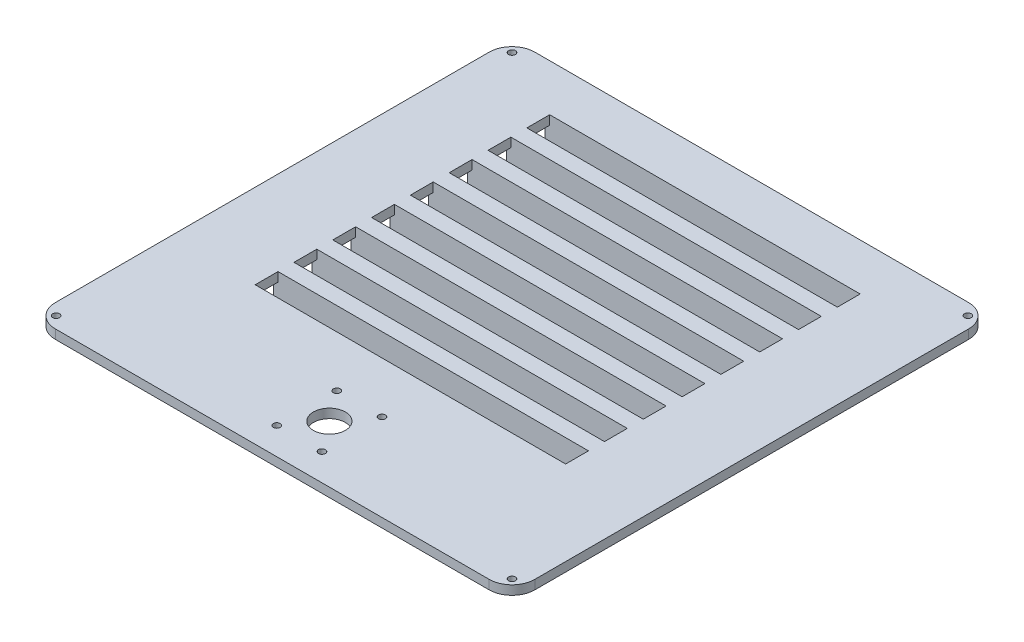
SolidWorks part; units mm, degrees
ref_plane "Front Plane" through (0, 0, 0) normal (0, 0, 1) x (1, 0, 0)
ref_plane "Top Plane" through (0, 0, 0) normal (0, 1, 0) x (1, 0, 0)
ref_plane "Right Plane" through (0, 0, 0) normal (1, 0, 0) x (0, 0, -1)
sketch "Sketch1" plane through (0, 0, 0) normal (0, 1, 0) x (1, 0, 0)
  line L0 (-101, -101) -> (-101, 101)
  line L5 (-105, -105) -> (105, -105)
  line L6 (-105, -105) -> (-105, 105)
  line L7 (-105, 105) -> (105, 105)
  line L8 (105, -105) -> (105, 105)
  line L9 (-101, 101) -> (101, 101)
  line L10 (101, -101) -> (101, 101)
  line L11 (-101, -101) -> (101, -101)
  line L12 (-101, 101) -> (-99.8333, 99.8333) construction
  line L13 (-55, 0) -> (55, 0) construction
  line L14 (-101, -101) -> (-99.8333, -99.8333) construction
  line L15 (0, -55) -> (0, 55) construction
  line L16 (101, -101) -> (99.8333, -99.8333) construction
  line L17 (101, 101) -> (99.8333, 99.8333) construction
  circle A1 centre (-99.8333, 99.8333) radius 1.5
  circle A2 centre (-99.8333, -99.8333) radius 1.5
  circle A3 centre (99.8333, -99.8333) radius 1.5
  circle A4 centre (99.8333, 99.8333) radius 1.5
  point P0 (0, 0)
  point P6 (-105, 0)
  point P7 (0, 105)
  dimension "D3" = 4
  dimension "D4" = 3
  dimension "D1" = 210
  dimension "D2" = 210
  dimension "D5" = 1.65
  dimension "D6" = 45
extrude "MainExtrude" add sketch "Sketch1" along normal blind 4 contours L6 L5 L8 L7
extrude "ScrewHoles" cut sketch "Sketch1<6>" along normal up to surface (4 mm away) contours A1 | A2 | A3 | A4 up to face at (0, 4, 0)
sketch "Sketch1<6>" plane through (0, 0, 0) normal (0, 1, 0) x (1, 0, 0) same geometry as "Sketch1"
fillet "RoundedCorners" radius 10 4 edges at (-105, 2, -105) (-105, 2, 105) (105, 2, -105) (105, 2, 105)
sketch "Sketch3" plane through (0, 0, 0) normal (0, 1, 0) x (1, 0, 0)
  line L145 (-68, 96.5) -> (68, 96.5) construction
  line L146 (-68, 96.5) -> (-68, -56.5) construction
  line L147 (-68, -56.5) -> (68, -56.5) construction
  line L148 (68, 96.5) -> (68, -56.5) construction
  line L149 (-68, 96.5) -> (68, -56.5) construction
  line L151 (68, 96.5) -> (-68, -56.5) construction
  line L152 (-68, 79.5) -> (68, 79.5) construction
  line L154 (-68, 62.5) -> (68, 62.5) construction
  line L155 (-68, 45.5) -> (68, 45.5) construction
  line L157 (-68, 28.5) -> (68, 28.5) construction
  line L158 (-68, 11.5) -> (68, 11.5) construction
  line L159 (-68, -5.5) -> (68, -5.5) construction
  line L160 (-68, -22.5) -> (68, -22.5) construction
  line L161 (-68, -39.5) -> (68, -39.5) construction
  line L162 (-68, 74.5) -> (68, 74.5)
  line L163 (-68, 57.5) -> (68, 57.5)
  line L164 (-68, 40.5) -> (68, 40.5)
  line L165 (-68, 23.5) -> (68, 23.5)
  line L166 (-68, 6.5) -> (68, 6.5)
  line L167 (-68, -10.5) -> (68, -10.5)
  line L168 (-68, -27.5) -> (68, -27.5)
  line L169 (-68, -44.5) -> (68, -44.5)
  line L170 (-68, 84.5) -> (68, 84.5)
  line L171 (-68, 67.5) -> (68, 67.5)
  line L172 (-68, 50.5) -> (68, 50.5)
  line L173 (-68, 33.5) -> (68, 33.5)
  line L174 (-68, 16.5) -> (68, 16.5)
  line L175 (-68, -0.5) -> (68, -0.5)
  line L176 (-68, -17.5) -> (68, -17.5)
  line L177 (-68, -34.5) -> (68, -34.5)
  line L178 (-68, 74.5) -> (-68, 84.5)
  line L179 (68, 74.5) -> (68, 84.5)
  line L180 (-68, 57.5) -> (-68, 67.5)
  line L181 (68, 57.5) -> (68, 67.5)
  line L182 (-68, 40.5) -> (-68, 50.5)
  line L183 (68, 40.5) -> (68, 50.5)
  line L184 (-68, 23.5) -> (-68, 33.5)
  line L185 (68, 23.5) -> (68, 33.5)
  line L186 (-68, 6.5) -> (-68, 16.5)
  line L187 (68, 6.5) -> (68, 16.5)
  line L188 (-68, -10.5) -> (-68, -0.5)
  line L189 (68, -10.5) -> (68, -0.5)
  line L190 (-68, -27.5) -> (-68, -17.5)
  line L191 (68, -27.5) -> (68, -17.5)
  line L192 (-68, -44.5) -> (-68, -34.5)
  line L193 (68, -44.5) -> (68, -34.5)
  line L200 (-9.9, -66.85) -> (-9.9, -93.15) construction
  line L201 (-95, -105) -> (95, -105) construction
  line L207 (-97.2358, 20) -> (95.5763, 20) construction
  line L208 (-9.9, -66.85) -> (9.9, -66.85) construction
  circle A0 centre (0, -80) radius 7
  circle A1 centre (-9.9, -66.85) radius 1.5
  circle A2 centre (-9.9, -93.15) radius 1.5
  circle A3 centre (9.9, -93.15) radius 1.5
  circle A4 centre (9.9, -66.85) radius 1.5
  point P56 (-9.9, -80)
  point P69 (0, -66.85)
  point P70 (0, 20)
  dimension "D18" = 14
  dimension "D19" = 25
  dimension "D21" = 35.5
  dimension "D25" = 3
  dimension "D26" = 3
  dimension "D27" = 19.8
  dimension "D1" = 136
  dimension "D2" = 153
  dimension "D3" = 17
  dimension "D4" = 17
  dimension "D5" = 17
  dimension "D6" = 17
  dimension "D7" = 17
  dimension "D8" = 17
  dimension "D9" = 17
  dimension "D11" = 17
  dimension "D13" = 5
  dimension "D14" = 129
  dimension "D10" = 17
  dimension "D12" = 5
  dimension "D20" = 20
  dimension "D28" = 26.3
extrude "Trench" cut sketch "Sketch3" along normal blind 10
sketch "Sketch4" plane through (0, 0, 0) normal (0, 1, 0) x (1, 0, 0)
  line L0 (68, -34.5) -> (68, -44.5) construction
  line L1 (68, -44.5) -> (-68, -44.5) construction
  line L2 (-68, -44.5) -> (-68, -34.5) construction
  line L3 (-68, -34.5) -> (68, -34.5) construction
  line L4 (68, -17.5) -> (68, -27.5) construction
  line L5 (68, -27.5) -> (-68, -27.5) construction
  line L6 (-68, -27.5) -> (-68, -17.5) construction
  line L7 (-68, -17.5) -> (68, -17.5) construction
  line L8 (68, -0.5) -> (68, -10.5) construction
  line L9 (68, -10.5) -> (-68, -10.5) construction
  line L10 (-68, -10.5) -> (-68, -0.5) construction
  line L11 (-68, -0.5) -> (68, -0.5) construction
  line L12 (68, 16.5) -> (68, 6.5) construction
  line L13 (68, 6.5) -> (-68, 6.5) construction
  line L14 (-68, 6.5) -> (-68, 16.5) construction
  line L15 (-68, 16.5) -> (68, 16.5) construction
  line L16 (68, 33.5) -> (68, 23.5) construction
  line L17 (68, 23.5) -> (-68, 23.5) construction
  line L18 (-68, 23.5) -> (-68, 33.5) construction
  line L19 (-68, 33.5) -> (68, 33.5) construction
  line L20 (68, 50.5) -> (68, 40.5) construction
  line L21 (68, 40.5) -> (-68, 40.5) construction
  line L22 (-68, 40.5) -> (-68, 50.5) construction
  line L23 (-68, 50.5) -> (68, 50.5) construction
  line L24 (68, 67.5) -> (68, 57.5) construction
  line L25 (68, 57.5) -> (-68, 57.5) construction
  line L26 (-68, 57.5) -> (-68, 67.5) construction
  line L27 (-68, 67.5) -> (68, 67.5) construction
  line L28 (68, 84.5) -> (68, 74.5) construction
  line L29 (68, 74.5) -> (-68, 74.5) construction
  line L30 (-68, 74.5) -> (-68, 84.5) construction
  line L31 (-68, 84.5) -> (68, 84.5) construction
  line L32 (68, -34.5) -> (68, -44.5)
  line L33 (68, -44.5) -> (-68, -44.5)
  line L34 (-68, -44.5) -> (-68, -34.5)
  line L35 (-68, -34.5) -> (68, -34.5)
  line L36 (68, -17.5) -> (68, -27.5)
  line L37 (68, -27.5) -> (-68, -27.5)
  line L38 (-68, -27.5) -> (-68, -17.5)
  line L39 (-68, -17.5) -> (68, -17.5)
  line L40 (68, -0.5) -> (68, -10.5)
  line L41 (68, -10.5) -> (-68, -10.5)
  line L42 (-68, -10.5) -> (-68, -0.5)
  line L43 (-68, -0.5) -> (68, -0.5)
  line L44 (68, 16.5) -> (68, 6.5)
  line L45 (68, 6.5) -> (-68, 6.5)
  line L46 (-68, 6.5) -> (-68, 16.5)
  line L47 (-68, 16.5) -> (68, 16.5)
  line L48 (68, 33.5) -> (68, 23.5)
  line L49 (68, 23.5) -> (-68, 23.5)
  line L50 (-68, 23.5) -> (-68, 33.5)
  line L51 (-68, 33.5) -> (68, 33.5)
  line L52 (68, 50.5) -> (68, 40.5)
  line L53 (68, 40.5) -> (-68, 40.5)
  line L54 (-68, 40.5) -> (-68, 50.5)
  line L55 (-68, 50.5) -> (68, 50.5)
  line L56 (68, 67.5) -> (68, 57.5)
  line L57 (68, 57.5) -> (-68, 57.5)
  line L58 (-68, 57.5) -> (-68, 67.5)
  line L59 (-68, 67.5) -> (68, 67.5)
  line L60 (68, 84.5) -> (68, 74.5)
  line L61 (68, 74.5) -> (-68, 74.5)
  line L62 (-68, 74.5) -> (-68, 84.5)
  line L63 (-68, 84.5) -> (68, 84.5)
  line L64 (70, 86.5) -> (70, 72.5)
  line L65 (70, 72.5) -> (-70, 72.5)
  line L66 (-70, 72.5) -> (-70, 86.5)
  line L67 (-70, 86.5) -> (70, 86.5)
  line L68 (70, 69.5) -> (70, 55.5)
  line L69 (70, 55.5) -> (-70, 55.5)
  line L70 (-70, 55.5) -> (-70, 69.5)
  line L71 (-70, 69.5) -> (70, 69.5)
  line L72 (70, 52.5) -> (70, 38.5)
  line L73 (70, 38.5) -> (-70, 38.5)
  line L74 (-70, 38.5) -> (-70, 52.5)
  line L75 (-70, 52.5) -> (70, 52.5)
  line L76 (70, 35.5) -> (70, 21.5)
  line L77 (70, 21.5) -> (-70, 21.5)
  line L78 (-70, 21.5) -> (-70, 35.5)
  line L79 (-70, 35.5) -> (70, 35.5)
  line L80 (70, 18.5) -> (70, 4.5)
  line L81 (70, 4.5) -> (-70, 4.5)
  line L82 (-70, 4.5) -> (-70, 18.5)
  line L83 (-70, 18.5) -> (70, 18.5)
  line L84 (70, 1.5) -> (70, -12.5)
  line L85 (70, -12.5) -> (-70, -12.5)
  line L86 (-70, -12.5) -> (-70, 1.5)
  line L87 (-70, 1.5) -> (70, 1.5)
  line L88 (70, -15.5) -> (70, -29.5)
  line L89 (70, -29.5) -> (-70, -29.5)
  line L90 (-70, -29.5) -> (-70, -15.5)
  line L91 (-70, -15.5) -> (70, -15.5)
  line L92 (70, -32.5) -> (70, -46.5)
  line L93 (70, -46.5) -> (-70, -46.5)
  line L94 (-70, -46.5) -> (-70, -32.5)
  line L95 (-70, -32.5) -> (70, -32.5)
  dimension "D1" = 2
extrude "Trench Walls" add sketch "Sketch4" against normal blind 4
sketch "Sketch5" plane through (0, -4, 0) normal (0, -1, 0) x (1, 0, 0)
  line L0 (-70, -86.5) -> (70, -86.5) construction
  line L1 (70, -86.5) -> (70, -72.5) construction
  line L2 (70, -72.5) -> (-70, -72.5) construction
  line L3 (-70, -72.5) -> (-70, -86.5) construction
  line L4 (-70, -69.5) -> (70, -69.5) construction
  line L5 (70, -69.5) -> (70, -55.5) construction
  line L6 (70, -55.5) -> (-70, -55.5) construction
  line L7 (-70, -55.5) -> (-70, -69.5) construction
  line L8 (-70, -52.5) -> (70, -52.5) construction
  line L9 (70, -52.5) -> (70, -38.5) construction
  line L10 (70, -38.5) -> (-70, -38.5) construction
  line L11 (-70, -38.5) -> (-70, -52.5) construction
  line L12 (-70, -35.5) -> (70, -35.5) construction
  line L13 (70, -35.5) -> (70, -21.5) construction
  line L14 (70, -21.5) -> (-70, -21.5) construction
  line L15 (-70, -21.5) -> (-70, -35.5) construction
  line L16 (-70, -18.5) -> (70, -18.5) construction
  line L17 (70, -18.5) -> (70, -4.5) construction
  line L18 (70, -4.5) -> (-70, -4.5) construction
  line L19 (-70, -4.5) -> (-70, -18.5) construction
  line L20 (-70, -1.5) -> (70, -1.5) construction
  line L21 (70, -1.5) -> (70, 12.5) construction
  line L22 (70, 12.5) -> (-70, 12.5) construction
  line L23 (-70, 12.5) -> (-70, -1.5) construction
  line L24 (-70, 15.5) -> (70, 15.5) construction
  line L25 (70, 15.5) -> (70, 29.5) construction
  line L26 (70, 29.5) -> (-70, 29.5) construction
  line L27 (-70, 29.5) -> (-70, 15.5) construction
  line L28 (-70, 32.5) -> (70, 32.5) construction
  line L29 (70, 32.5) -> (70, 46.5) construction
  line L30 (70, 46.5) -> (-70, 46.5) construction
  line L31 (-70, 46.5) -> (-70, 32.5) construction
  line L32 (-70, -86.5) -> (70, -86.5)
  line L33 (70, -86.5) -> (70, -72.5)
  line L34 (70, -72.5) -> (-70, -72.5)
  line L35 (-70, -72.5) -> (-70, -86.5)
  line L36 (-70, -69.5) -> (70, -69.5)
  line L37 (70, -69.5) -> (70, -55.5)
  line L38 (70, -55.5) -> (-70, -55.5)
  line L39 (-70, -55.5) -> (-70, -69.5)
  line L40 (-70, -52.5) -> (70, -52.5)
  line L41 (70, -52.5) -> (70, -38.5)
  line L42 (70, -38.5) -> (-70, -38.5)
  line L43 (-70, -38.5) -> (-70, -52.5)
  line L44 (-70, -35.5) -> (70, -35.5)
  line L45 (70, -35.5) -> (70, -21.5)
  line L46 (70, -21.5) -> (-70, -21.5)
  line L47 (-70, -21.5) -> (-70, -35.5)
  line L48 (-70, -18.5) -> (70, -18.5)
  line L49 (70, -18.5) -> (70, -4.5)
  line L50 (70, -4.5) -> (-70, -4.5)
  line L51 (-70, -4.5) -> (-70, -18.5)
  line L52 (-70, -1.5) -> (70, -1.5)
  line L53 (70, -1.5) -> (70, 12.5)
  line L54 (70, 12.5) -> (-70, 12.5)
  line L55 (-70, 12.5) -> (-70, -1.5)
  line L56 (-70, 15.5) -> (70, 15.5)
  line L57 (70, 15.5) -> (70, 29.5)
  line L58 (70, 29.5) -> (-70, 29.5)
  line L59 (-70, 29.5) -> (-70, 15.5)
  line L60 (-70, 32.5) -> (70, 32.5)
  line L61 (70, 32.5) -> (70, 46.5)
  line L62 (70, 46.5) -> (-70, 46.5)
  line L63 (-70, 46.5) -> (-70, 32.5)
extrude "Trench Bottom" add sketch "Sketch5" along normal blind 2
sketch "Sketch7" plane through (70, 0, 0) normal (1, 0, 0) x (0, 0, -1)
  line L1 (-44.5, 0) -> (-34.5, 0)
  line L2 (-44.5, 0) -> (-44.5, -6)
  line L3 (-44.5, -6) -> (-34.5, -6)
  line L4 (-34.5, 0) -> (-34.5, -6)
  line L5 (-46.5, -6) -> (-46.5, 0) construction
  line L6 (-32.5, -6) -> (-46.5, -6) construction
  line L7 (-27.5, 0) -> (-27.5, -6)
  line L8 (-27.5, 0) -> (-17.5, 0)
  line L9 (-17.5, 0) -> (-17.5, -6)
  line L10 (-27.5, -6) -> (-17.5, -6)
  line L11 (-10.5, 0) -> (-10.5, -6)
  line L12 (-10.5, 0) -> (-0.5, 0)
  line L13 (-0.5, 0) -> (-0.5, -6)
  line L14 (-10.5, -6) -> (-0.5, -6)
  line L15 (6.5, 0) -> (6.5, -6)
  line L16 (6.5, 0) -> (16.5, 0)
  line L17 (16.5, 0) -> (16.5, -6)
  line L18 (6.5, -6) -> (16.5, -6)
  line L19 (23.5, 0) -> (23.5, -6)
  line L20 (23.5, 0) -> (33.5, 0)
  line L21 (33.5, 0) -> (33.5, -6)
  line L22 (23.5, -6) -> (33.5, -6)
  line L23 (40.5, 0) -> (40.5, -6)
  line L24 (40.5, 0) -> (50.5, 0)
  line L25 (50.5, 0) -> (50.5, -6)
  line L26 (40.5, -6) -> (50.5, -6)
  line L27 (57.5, 0) -> (57.5, -6)
  line L28 (57.5, 0) -> (67.5, 0)
  line L29 (67.5, 0) -> (67.5, -6)
  line L30 (57.5, -6) -> (67.5, -6)
  line L31 (74.5, 0) -> (74.5, -6)
  line L32 (74.5, 0) -> (84.5, 0)
  line L33 (84.5, 0) -> (84.5, -6)
  line L34 (74.5, -6) -> (84.5, -6)
  line L35 (-29.5, -6) -> (-29.5, 0) construction
  line L36 (-46.5, 0) -> (-32.5, 0) construction
  dimension "D3" = 10
  dimension "D4" = 2
  dimension "D5" = 8
  dimension "D6" = 2
extrude "Wire Opening" cut sketch "Sketch7" against normal through all both and the other way through all
sketch "Sketch9" plane through (0, 0, 0) normal (0, -1, 0) x (1, 0, 0)
  line L0 (-95, 105) -> (95, 105) construction
  line L1 (-70, 46.5) -> (70, 46.5) construction
  line L5 (-105, 95) -> (-105, -95) construction
  circle A0 centre (-94, 92) radius 0.98
  circle A1 centre (-94, 92) radius 2
  circle A2 centre (-19.73, 92) radius 2
  circle A3 centre (-19.73, 92) radius 0.98
  circle A4 centre (-94, 56.16) radius 2
  circle A5 centre (-94, 56.16) radius 0.98
  circle A6 centre (-19.73, 56.16) radius 0.98
  circle A7 centre (-19.73, 56.16) radius 2
  circle A8 centre (-99.8333, 99.8333) radius 1.5 construction
  dimension "D1" = 13
  dimension "D2" = 35.84
  dimension "D5" = 1.96
  dimension "D6" = 4
  dimension "D7" = 1.96
  dimension "D8" = 4
  dimension "D3" = 11
  dimension "D4" = 74.27
  dimension "D9" = 9.7666
  dimension "D10" = 9.66
extrude "PCB Holes" add sketch "Sketch9" along normal blind 4
fillet "PCB Rounds" radius 2 4 edges at (-19.73, 0, 58.16) (-19.73, 0, 94) (-94, 0, 58.16) (-94, 0, 94)
equation "\"1_LED\"= 17mm"
equation "\"2_LED\"= \"1_LED\" * 2"
equation "\"3_LED\"= \"1_LED\" * 3"
equation "\"4_LED\"= \"1_LED\" * 4"
equation "\"5_LED\"= \"1_LED\" * 5"
equation "\"6_LED\"= \"1_LED\" * 6"
equation "\"7_LED\"= \"1_LED\" * 7"
equation "\"8_LED\"= \"1_LED\" * 8"
equation "\"9_LED\"= \"1_LED\" * 9"
equation "\"10_LED\"= \"1_LED\" * 10"
equation "\"11_LED\"= \"1_LED\" * 11"
equation "\"12_LED\"= \"1_LED\" * 12"
